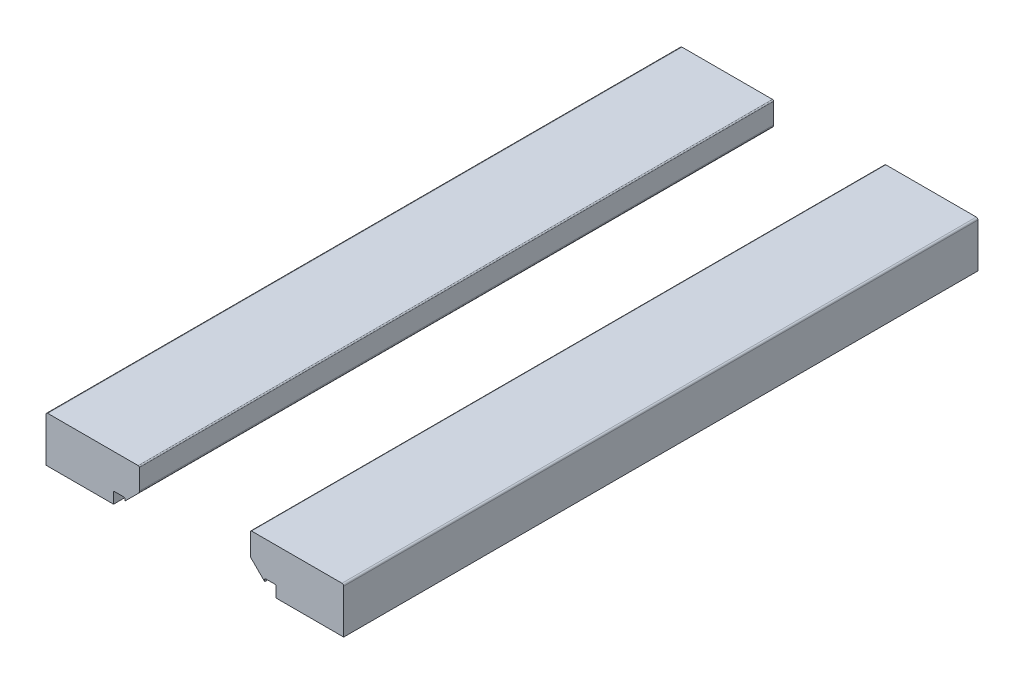
SolidWorks part; units mm, degrees
material "PE High Density"
ref_plane "Front Plane" through (0, 0, 0) normal (0, 0, 1) x (1, 0, 0)
ref_plane "Top Plane" through (0, 0, 0) normal (0, 1, 0) x (1, 0, 0)
ref_plane "Right Plane" through (0, 0, 0) normal (1, 0, 0) x (0, 0, -1)
sketch "Retainer Profile" plane through (0, 0, 0) normal (0, 0, 1) x (1, 0, 0)
  line L47 (0, 0) -> (0, 20) construction
  line L64 (13, 8.15) -> (13, 4.3)
  line L67 (-4.9379, 6.2036) -> (-6.1, 5.0414)
  line L68 (-6.1, 5.2) -> (-6.1, 5.0414)
  line L69 (-7, 5.3) -> (-6.2, 5.3)
  line L70 (-7.1, 4.3) -> (-7.1, 5.2)
  line L74 (-7.1, 4.3) -> (-13, 4.3)
  line L75 (-13, 8.15) -> (-13, 4.3)
  line L78 (7.1, 4.3) -> (13, 4.3)
  line L79 (4.95, 8.3) -> (12.85, 8.3)
  line L80 (7.1, 4.3) -> (7.1, 5.2)
  line L81 (7, 5.3) -> (6.2, 5.3)
  line L82 (6.1, 5.2) -> (6.1, 5.0414)
  line L83 (4.85, 8.2) -> (4.85, 6.4157)
  line L84 (4.9379, 6.2036) -> (6.1, 5.0414)
  line L85 (-4.95, 8.3) -> (-12.85, 8.3)
  line L86 (-4.85, 8.2) -> (-4.85, 6.4157)
  arc A31 (7, 5.3) -> (7.1, 5.2) centre (7, 5.2) cw
  arc A32 (6.1, 5.2) -> (6.2, 5.3) centre (6.2, 5.2) cw
  arc A34 (4.85, 8.2) -> (4.95, 8.3) centre (4.95, 8.2) cw
  arc A35 (4.85, 6.4157) -> (4.9379, 6.2036) centre (5.15, 6.4157) ccw
  arc A36 (12.85, 8.3) -> (13, 8.15) centre (12.85, 8.15) cw
  arc A37 (-4.85, 6.4157) -> (-4.9379, 6.2036) centre (-5.15, 6.4157) cw
  arc A38 (-6.1, 5.2) -> (-6.2, 5.3) centre (-6.2, 5.2) ccw
  arc A39 (-7, 5.3) -> (-7.1, 5.2) centre (-7, 5.2) ccw
  arc A40 (-12.85, 8.3) -> (-13, 8.15) centre (-12.85, 8.15) ccw
  arc A41 (-4.85, 8.2) -> (-4.95, 8.3) centre (-4.95, 8.2) ccw
  point P89 (7.1, 5.3)
  point P93 (7.1, 4.3)
  dimension "D10" = 2.25
  dimension "D11" = 1.8843
  dimension "D12" = 0.15
  dimension "D5" = 1
  dimension "D6" = 225
  dimension "D1" = 4.3
  dimension "D2" = 4
  dimension "D3" = 1
  dimension "D4" = 0.1
  dimension "D7" = 0.3
  dimension "D8" = 4.85
  dimension "D9" = 13
extrude "Retainers" add sketch "Retainer Profile" against normal mid plane 55.4
